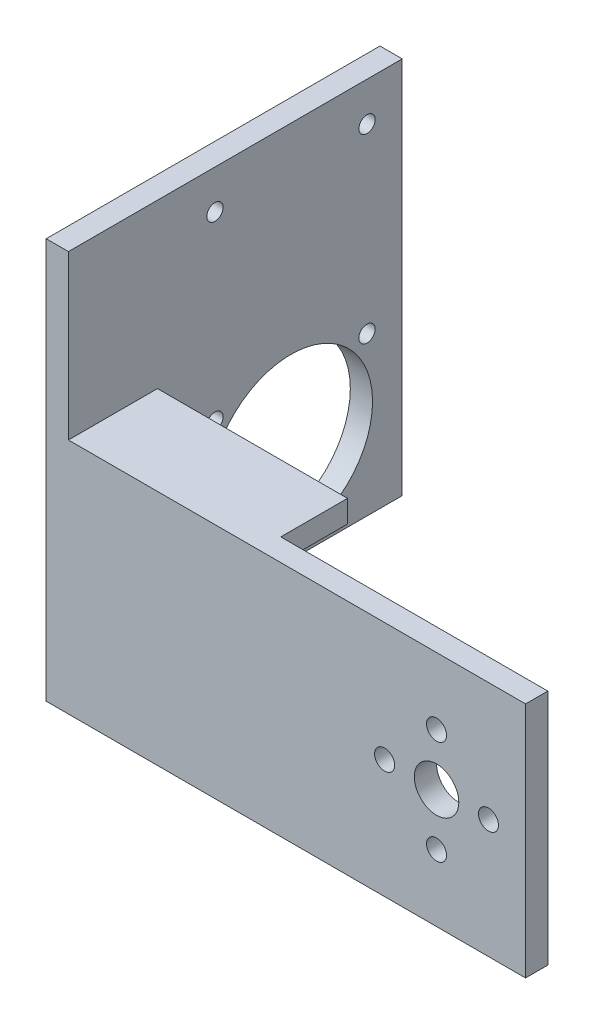
SolidWorks part; units mm, degrees
ref_plane "Front Plane" through (0, 0, 0) normal (0, 0, 1) x (1, 0, 0)
ref_plane "Top Plane" through (0, 0, 0) normal (0, 1, 0) x (1, 0, 0)
ref_plane "Right Plane" through (0, 0, 0) normal (1, 0, 0) x (0, 0, -1)
ref_plane "PZ_p27_000" through (0, 0, 27) normal (0, 0, 1) x (1, 0, 0)
sketch "S_box1" plane through (0, 0, 27) normal (0, 0, 1) x (1, 0, 0)
  line L0 (-52.625, -16) -> (12, -16)
  line L1 (12, -16) -> (12, 16)
  line L2 (12, 16) -> (-52.625, 16)
  line L3 (-52.625, 16) -> (-52.625, -16)
  dimension "P1" = 52.625
  dimension "P2" = 16
  dimension "P3" = 12
  dimension "P4" = 16
  dimension "P5" = 12
  dimension "P6" = 16
  dimension "P7" = 52.625
  dimension "P8" = 16
extrude "Boss_1" add sketch "S_box1" along normal blind 3
ref_plane "PZ_m15_000" through (0, 0, -15) normal (0, 0, 1) x (1, 0, 0)
sketch "S_box2" plane through (0, 0, -15) normal (0, 0, 1) x (1, 0, 0)
  line L0 (-52.625, -13) -> (-49.625, -13)
  line L1 (-49.625, -13) -> (-49.625, 38)
  line L2 (-49.625, 38) -> (-52.625, 38)
  line L3 (-52.625, 38) -> (-52.625, -13)
  dimension "P1" = 52.625
  dimension "P2" = 13
  dimension "P3" = 49.625
  dimension "P4" = 13
  dimension "P5" = 49.625
  dimension "P6" = 38
  dimension "P7" = 52.625
  dimension "P8" = 38
extrude "Boss_2" add sketch "S_box2" along normal blind 45
ref_plane "PZ_p18_000" through (0, 0, 18) normal (0, 0, 1) x (1, 0, 0)
sketch "S_box3" plane through (0, 0, 18) normal (0, 0, 1) x (1, 0, 0)
  line L0 (-50.125, -13.5) -> (-24, -13.5)
  line L1 (-24, -13.5) -> (-24, -10.5)
  line L2 (-24, -10.5) -> (-50.125, -10.5)
  line L3 (-50.125, -10.5) -> (-50.125, -13.5)
  dimension "P1" = 50.125
  dimension "P2" = 13.5
  dimension "P3" = 24
  dimension "P4" = 13.5
  dimension "P5" = 24
  dimension "P6" = 10.5
  dimension "P7" = 50.125
  dimension "P8" = 10.5
extrude "Boss_3" add sketch "S_box3" along normal blind 11.5
sketch "S_box4" plane through (0, 0, 18) normal (0, 0, 1) x (1, 0, 0)
  line L0 (-50.125, 13) -> (-24, 13)
  line L1 (-24, 13) -> (-24, 16)
  line L2 (-24, 16) -> (-50.125, 16)
  line L3 (-50.125, 16) -> (-50.125, 13)
  dimension "P1" = 50.125
  dimension "P2" = 13
  dimension "P3" = 24
  dimension "P4" = 13
  dimension "P5" = 24
  dimension "P6" = 16
  dimension "P7" = 50.125
  dimension "P8" = 16
extrude "Boss_4" add sketch "S_box4" along normal blind 11.5
ref_plane "PZ_p26_900" through (0, 0, 26.9) normal (0, 0, 1) x (1, 0, 0)
sketch "S_hole5" plane through (0, 0, 26.9) normal (0, 0, 1) x (1, 0, 0)
  circle A0 centre (0, 0) radius 3
  dimension "D1_S_hole5" = 6
extrude "Hole_5" cut sketch "S_hole5" along normal blind 3.2
sketch "S_hole6" plane through (0, 0, 26.9) normal (0, 0, 1) x (1, 0, 0)
  circle A0 centre (7, 0) radius 1.35
  dimension "D1_S_hole6" = 2.7
  dimension "P2" = 7
extrude "Hole_6" cut sketch "S_hole6" along normal blind 3.2
sketch "S_hole7" plane through (0, 0, 26.9) normal (0, 0, 1) x (1, 0, 0)
  circle A0 centre (0, -7) radius 1.35
  dimension "D1_S_hole7" = 2.7
  dimension "P2" = 7
extrude "Hole_7" cut sketch "S_hole7" along normal blind 3.2
sketch "S_hole8" plane through (0, 0, 26.9) normal (0, 0, 1) x (1, 0, 0)
  circle A0 centre (-7, 0) radius 1.35
  dimension "D1_S_hole8" = 2.7
  dimension "P2" = 7
extrude "Hole_8" cut sketch "S_hole8" along normal blind 3.2
sketch "S_hole9" plane through (0, 0, 26.9) normal (0, 0, 1) x (1, 0, 0)
  circle A0 centre (0, 7) radius 1.35
  dimension "D1_S_hole9" = 2.7
  dimension "P2" = 7
extrude "Hole_9" cut sketch "S_hole9" along normal blind 3.2
ref_plane "PX_m52_725" through (-52.725, 0, 0) normal (1, 0, 0) x (0, 0, -1)
sketch "S_hole10" plane through (-52.725, 0, 0) normal (1, 0, 0) x (0, 0, -1)
  circle A0 centre (0, 0) radius 11
  dimension "D1_S_hole10" = 22
extrude "Hole_10" cut sketch "S_hole10" along normal blind 3.2
sketch "S_hole11" plane through (-52.725, 0, 0) normal (1, 0, 0) x (0, 0, -1)
  circle A0 centre (10.25, 8.3) radius 1.1
  dimension "D1_S_hole11" = 2.2
  dimension "P2" = 10.25
  dimension "P3" = 8.3
extrude "Hole_11" cut sketch "S_hole11" along normal blind 3.2
sketch "S_hole12" plane through (-52.725, 0, 0) normal (1, 0, 0) x (0, 0, -1)
  circle A0 centre (-10.25, 8.3) radius 1.1
  dimension "D1_S_hole12" = 2.2
  dimension "P2" = 10.25
  dimension "P3" = 8.3
extrude "Hole_12" cut sketch "S_hole12" along normal blind 3.2
sketch "S_hole13" plane through (-52.725, 0, 0) normal (1, 0, 0) x (0, 0, -1)
  circle A0 centre (10.25, 32.75) radius 1.1
  dimension "D1_S_hole13" = 2.2
  dimension "P2" = 10.25
  dimension "P3" = 32.75
extrude "Hole_13" cut sketch "S_hole13" along normal blind 3.2
sketch "S_hole14" plane through (-52.725, 0, 0) normal (1, 0, 0) x (0, 0, -1)
  circle A0 centre (-10.25, 32.75) radius 1.1
  dimension "D1_S_hole14" = 2.2
  dimension "P2" = 10.25
  dimension "P3" = 32.75
extrude "Hole_14" cut sketch "S_hole14" along normal blind 3.2
equation "\"plate_t\" = 3"
equation "\"clearance\" = 0.4"
